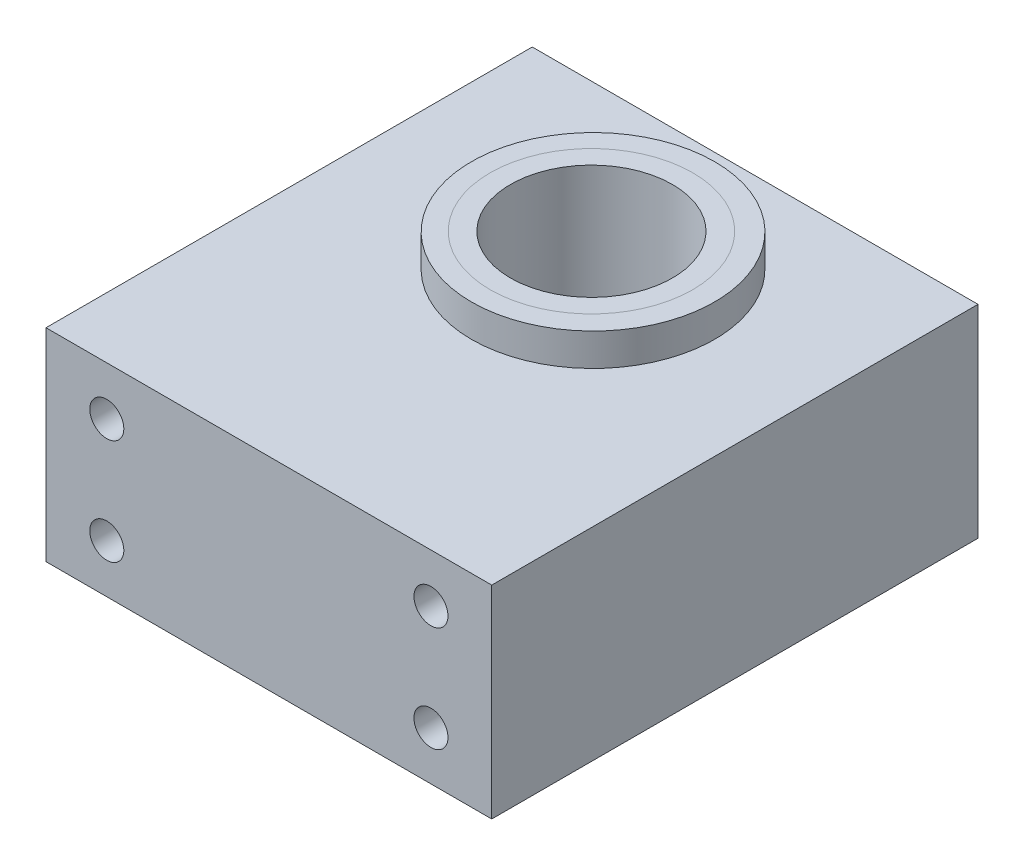
SolidWorks part; units mm, degrees
material "AISI 1020"
ref_plane "Front Plane" through (0, 0, 0) normal (0, 0, 1) x (1, 0, 0)
ref_plane "Top Plane" through (0, 0, 0) normal (0, 1, 0) x (1, 0, 0)
ref_plane "Right Plane" through (0, 0, 0) normal (1, 0, 0) x (0, 0, -1)
sketch "Sketch1" plane through (0, 0, 0) normal (0, 1, 0) x (1, 0, 0)
  line L1 (-55, 40) -> (55, 40)
  line L2 (-55, 40) -> (-55, -80)
  line L3 (-55, -80) -> (55, -80)
  line L4 (55, 40) -> (55, -80)
  dimension "D1" = 55
  dimension "D2" = 40
  dimension "D3" = 55
  dimension "D4" = 80
extrude "GUIDE_BLOCK" add sketch "Sketch1" along normal blind 50
sketch "Sketch2" plane through (0, 50, 0) normal (0, 1, 0) x (1, 0, 0)
  circle A0 centre (0, 0) radius 30
  circle A1 centre (-0.3162, -0.0775) radius 25
  dimension "D1" = 50
  dimension "D4" = 60
  dimension "D2" = 0.3162
  dimension "D3" = 0.0775
extrude "BUSH_BOSS" add sketch "Sketch2" along normal blind 8
sketch "Sketch3" plane through (0, 50, 0) normal (0, 1, 0) x (1, 0, 0)
  circle A0 centre (-0.3162, -0.0775) radius 25 construction
  circle A1 centre (-0.3162, -0.0775) radius 25
extrude "Cut-Extrude1" cut sketch "Sketch3" against normal through all
sketch "Sketch4" plane through (0, 0, -40) normal (0, 0, -1) x (-1, 0, 0)
  line L0 (-55, 50) -> (55, 50) construction
  line L1 (-55, 0) -> (55, 0) construction
  line L2 (-55, 50) -> (-55, 0) construction
  line L3 (55, 50) -> (55, 0) construction
  point P0 (-40, 38)
  point P1 (40, 38)
  point P2 (-40, 12)
  point P3 (40, 12)
  dimension "D1" = 12
  dimension "D2" = 12
  dimension "D3" = 15
  dimension "D4" = 15
  dimension "D5" = 12
  dimension "D6" = 15
  dimension "D7" = 12
  dimension "D8" = 15
hole_wizard "CBORE for M8 Hex Socket Head Cap Screw1" positions "Sketch4" profile "Sketch6" counterbore size "M8" standard "ISO" end condition through all
sketch "Sketch6" plane through (40, 38, -40) normal (1, 0, 0) x (0, 1, 0)
  line L0 (0, 0) -> (0, 120)
  line L1 (0, 120) -> (4.2, 120)
  line L3 (4.2, 120) -> (4.2, 8.6)
  line L4 (4.2, 8.6) -> (7.5, 8.6)
  line L5 (7.5, 8.6) -> (7.5, 0)
  line L7 (7.5, 0) -> (0, 0)
  line L11 (0, -6.35) -> (0, 107.95) construction
  dimension "Thru Hole Dia." = 8.4
  dimension "Thru Hole Depth" = 120
  dimension "C'Bore Dia." = 15
  dimension "C'Bore Depth" = 8.6
sketch "Sketch8" plane through (0, 0, 0) normal (0, 1, 0) x (1, 0, 0)
  circle A0 centre (-0.3162, -0.0775) radius 25 construction
  circle A1 centre (-0.3162, -0.0775) radius 25
  circle A2 centre (-0.3162, -0.0775) radius 20
  dimension "D1" = 40
extrude "Boss-Extrude3" add sketch "Sketch8" along normal up to surface (58 mm away) separate body up to face at (0, 58, 30)
ref_axis "BORE_AXIS" through (-0.3162, 58, 0.0775) along (0, -1, 0)
ref_axis "Axis2" through (-0.3162, 58, 0.0775) along (0, -1, 0)
